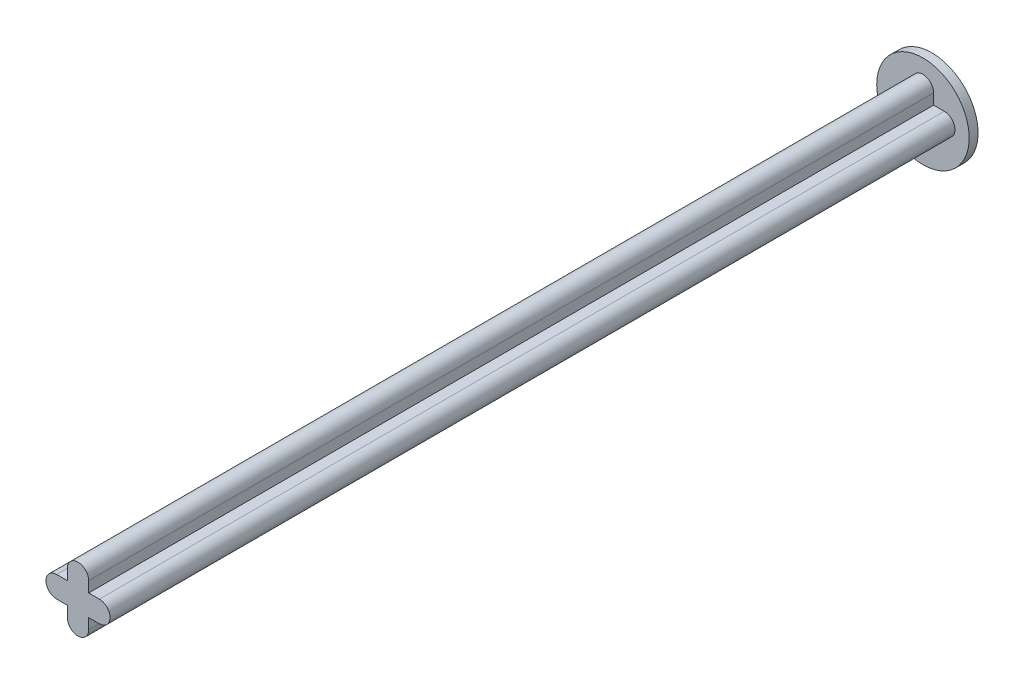
SolidWorks part; units mm, degrees
material "PVC Rigid"
ref_plane "Front Plane" through (0, 0, 0) normal (0, 0, 1) x (1, 0, 0)
ref_plane "Top Plane" through (0, 0, 0) normal (0, 1, 0) x (1, 0, 0)
ref_plane "Right Plane" through (0, 0, 0) normal (1, 0, 0) x (0, 0, -1)
sketch "Sketch1" plane through (0, 0, 0) normal (0, 0, 1) x (1, 0, 0)
  line L0 (0, 0) -> (3.048, 0) construction
  line L1 (0, 0.762) -> (3.048, 0.762)
  line L2 (0, -0.762) -> (3.048, -0.762)
  line L8 (1.524, 1.524) -> (1.524, -1.524) construction
  line L9 (2.286, 1.524) -> (2.286, -1.524)
  line L10 (0.762, 1.524) -> (0.762, -1.524)
  arc A0 (0, 0.762) -> (0, -0.762) centre (0, 0) ccw
  arc A2 (3.048, -0.762) -> (3.048, 0.762) centre (3.048, 0) ccw
  arc A4 (2.286, 1.524) -> (0.762, 1.524) centre (1.524, 1.524) ccw
  arc A5 (0.762, -1.524) -> (2.286, -1.524) centre (1.524, -1.524) ccw
  circle A7 centre (1.524, 0) radius 2.286 construction
  point P1 (3.81, 0)
  point P3 (1.524, 0)
  point P8 (1.524, 0)
  point P13 (5.334, 0)
  point P15 (7.62, 0)
  point P17 (0, 3.302)
  point P18 (19.05, 3.302)
  point P19 (0, -3.302)
  point P20 (19.05, -3.302)
  point P23 (13.843, 0)
  point P24 (3.81, 0)
  point P25 (23.368, 0)
  point P26 (3.429, 0)
  point P27 (-7.874, -3.302)
  point P28 (7.874, -3.302)
  point P29 (-7.874, 3.302)
  point P30 (7.874, 3.302)
  point P35 (11.811, 0)
  point P60 (11.5175, 1.1139)
  dimension "D2" = 1.524
  dimension "D3" = 4.572
  dimension "D1" = 1.524
extrude "Boss-Extrude1" add sketch "Sketch1" along normal blind 60.96 contours L1 A0 L2 L10 | L9 A4 L10 L1 | L2 A2 L1 L9 | L10 A5 L9 L2 | L1 L10 L2 L9 region at (0.0711, 0, 0) region at (1.524, 1.4529, 0) region at (1.524, 0, 0) region at (2.9769, 0, 0) region at (1.524, -1.4529, 0)
sketch "Sketch2" plane through (0, 0, 0) normal (0, 0, -1) x (-1, 0, 0)
  circle A0 centre (-1.524, 0) radius 3.302
extrude "Boss-Extrude2" add sketch "Sketch2" against normal blind 0.635
